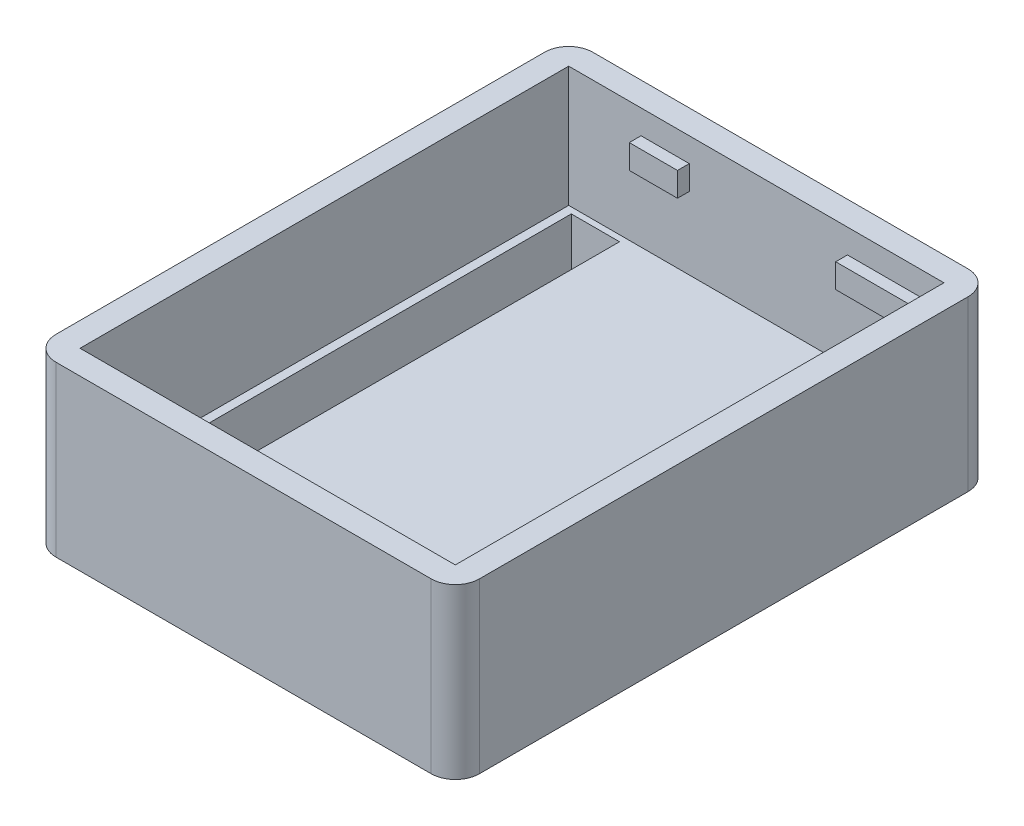
SolidWorks part; units mm, degrees
ref_plane "Plan de face" through (0, 0, 0) normal (0, 0, 1) x (1, 0, 0)
ref_plane "Plan de dessus" through (0, 0, 0) normal (0, 1, 0) x (1, 0, 0)
ref_plane "Plan de droite" through (0, 0, 0) normal (1, 0, 0) x (0, 0, -1)
sketch "Esquisse1" plane through (0, 0, 0) normal (0, 1, 0) x (1, 0, 0)
  line L1 (1, 0) -> (16.5601, 0)
  line L2 (0, 1) -> (0, 21.2618)
  line L3 (1, 22.2619) -> (16.5601, 22.2619)
  line L4 (17.5601, 1) -> (17.5601, 21.2618)
  arc A0 (16.5601, 0) -> (17.5601, 1) centre (16.5601, 1) ccw
  arc A1 (16.5601, 22.2619) -> (17.5601, 21.2618) centre (16.5601, 21.2619) cw
  arc A2 (0, 21.2618) -> (1, 22.2619) centre (1, 21.2619) cw
  arc A3 (1, 0) -> (0, 1) centre (1, 1) cw
  point P7 (17.5601, 0)
  point P12 (0, 22.2619)
  point P15 (0, 0)
  dimension "D3" = 1
  dimension "D1" = 22.2619
  dimension "D2" = 17.5601
extrude "Boss.-Extru.1" add sketch "Esquisse1" along normal blind 7 contours L1 A0 L4 A1 L3 A2 L2 A3
sketch "Esquisse2" plane through (0, 7, 0) normal (0, 1, 0) x (1, 0, 0)
  line L8 (1, 1) -> (16.5601, 1)
  line L9 (16.5601, 1) -> (16.5601, 21.2619)
  line L10 (16.5601, 21.2619) -> (1, 21.2619)
  line L11 (1, 21.2619) -> (1, 1)
  line L12 (1, 1) -> (16.5601, 1)
  line L13 (16.5601, 1) -> (16.5601, 21.2619)
  line L14 (16.5601, 21.2619) -> (1, 21.2619)
  line L15 (1, 21.2619) -> (1, 1)
  dimension "D1" = 1
extrude "Enlèv. mat.-Extru.1" cut sketch "Esquisse2" against normal blind 5
sketch "Esquisse5" plane through (0, 2, 0) normal (0, 1, 0) x (1, 0, 0)
  line L0 (1, 1) -> (16.5601, 1) construction
  line L1 (3.36, 21.01) -> (1.36, 21.01)
  line L2 (3.36, 21.01) -> (3.36, 1.25)
  line L3 (3.36, 1.25) -> (1.36, 1.25)
  line L4 (1.36, 21.01) -> (1.36, 1.25)
  line L5 (1, 21.2619) -> (1, 1) construction
  point P4 (1.7271, 10.9122)
  dimension "D1" = 19.76
  dimension "D2" = 2
  dimension "D3" = 0.25
  dimension "D4" = 0.36
extrude "Enlèv. mat.-Extru.3" cut sketch "Esquisse5" against normal through all
sketch "Esquisse6" plane through (0, 0, -21.2619) normal (0, 0, 1) x (1, 0, 0)
  line L0 (16.5601, 2) -> (16.5601, 7) construction
  line L1 (15.5601, 5) -> (12.5601, 5)
  line L2 (15.5601, 5) -> (15.5601, 6)
  line L3 (15.5601, 6) -> (12.5601, 6)
  line L4 (12.5601, 5) -> (12.5601, 6)
  line L5 (16.5601, 2) -> (1, 2) construction
  dimension "D1" = 3
  dimension "D2" = 1
  dimension "D3" = 1
  dimension "D4" = 3
extrude "Boss.-Extru.2" add sketch "Esquisse6" along normal blind 0.489
sketch "Esquisse7" plane through (16.5601, 0, 0) normal (-1, 0, 0) x (0, 0, 1)
  line L0 (-21.2619, 2) -> (-21.2619, 7) construction
  line L1 (-20.2619, 5) -> (-17.2619, 5)
  line L2 (-20.2619, 5) -> (-20.2619, 6)
  line L3 (-20.2619, 6) -> (-17.2619, 6)
  line L4 (-17.2619, 5) -> (-17.2619, 6)
  line L5 (-1, 2) -> (-21.2619, 2) construction
  dimension "D1" = 3
  dimension "D2" = 1
  dimension "D3" = 1
  dimension "D4" = 3
extrude "Boss.-Extru.3" add sketch "Esquisse7" along normal blind 0.489
sketch "Esquisse8" plane through (0, 0, -1) normal (0, 0, -1) x (-1, 0, 0)
  line L0 (-16.5601, 2) -> (-16.5601, 7) construction
  line L1 (-15.5601, 6) -> (-12.5601, 6)
  line L2 (-15.5601, 6) -> (-15.5601, 5)
  line L3 (-15.5601, 5) -> (-12.5601, 5)
  line L4 (-12.5601, 6) -> (-12.5601, 5)
  line L5 (-1, 2) -> (-16.5601, 2) construction
  dimension "D1" = 3
  dimension "D2" = 1
  dimension "D3" = 1
  dimension "D4" = 3
extrude "Boss.-Extru.4" add sketch "Esquisse8" along normal blind 0.489
sketch "Esquisse9" plane through (16.5601, 0, 0) normal (-1, 0, 0) x (0, 0, 1)
  line L0 (-1, 2) -> (-21.2619, 2) construction
  line L1 (-2, 6) -> (-5, 6)
  line L2 (-2, 6) -> (-2, 5)
  line L3 (-2, 5) -> (-5, 5)
  line L4 (-5, 6) -> (-5, 5)
  line L5 (-1, 2) -> (-1, 7) construction
  dimension "D1" = 3
  dimension "D2" = 1
  dimension "D3" = 3
  dimension "D4" = 1
extrude "Boss.-Extru.5" add sketch "Esquisse9" along normal blind 0.489
sketch "Esquisse10" plane through (0, 0, -21.2619) normal (0, 0, 1) x (1, 0, 0)
  line L0 (1, 2) -> (1, 7) construction
  line L1 (4, 5) -> (6, 5)
  line L2 (4, 5) -> (4, 6)
  line L3 (4, 6) -> (6, 6)
  line L4 (6, 5) -> (6, 6)
  line L5 (16.5601, 2) -> (1, 2) construction
  dimension "D1" = 2
  dimension "D2" = 1
  dimension "D3" = 3
  dimension "D4" = 3
extrude "Boss.-Extru.6" add sketch "Esquisse10" along normal blind 0.489
sketch "Esquisse11" plane through (0, 0, -1) normal (0, 0, -1) x (-1, 0, 0)
  line L0 (-1, 2) -> (-16.5601, 2) construction
  line L1 (-4, 6) -> (-6, 6)
  line L2 (-4, 6) -> (-4, 5)
  line L3 (-4, 5) -> (-6, 5)
  line L4 (-6, 6) -> (-6, 5)
  line L5 (-1, 2) -> (-1, 7) construction
  dimension "D1" = 2
  dimension "D2" = 1
  dimension "D3" = 3
  dimension "D4" = 3
extrude "Boss.-Extru.7" add sketch "Esquisse11" along normal blind 0.489
